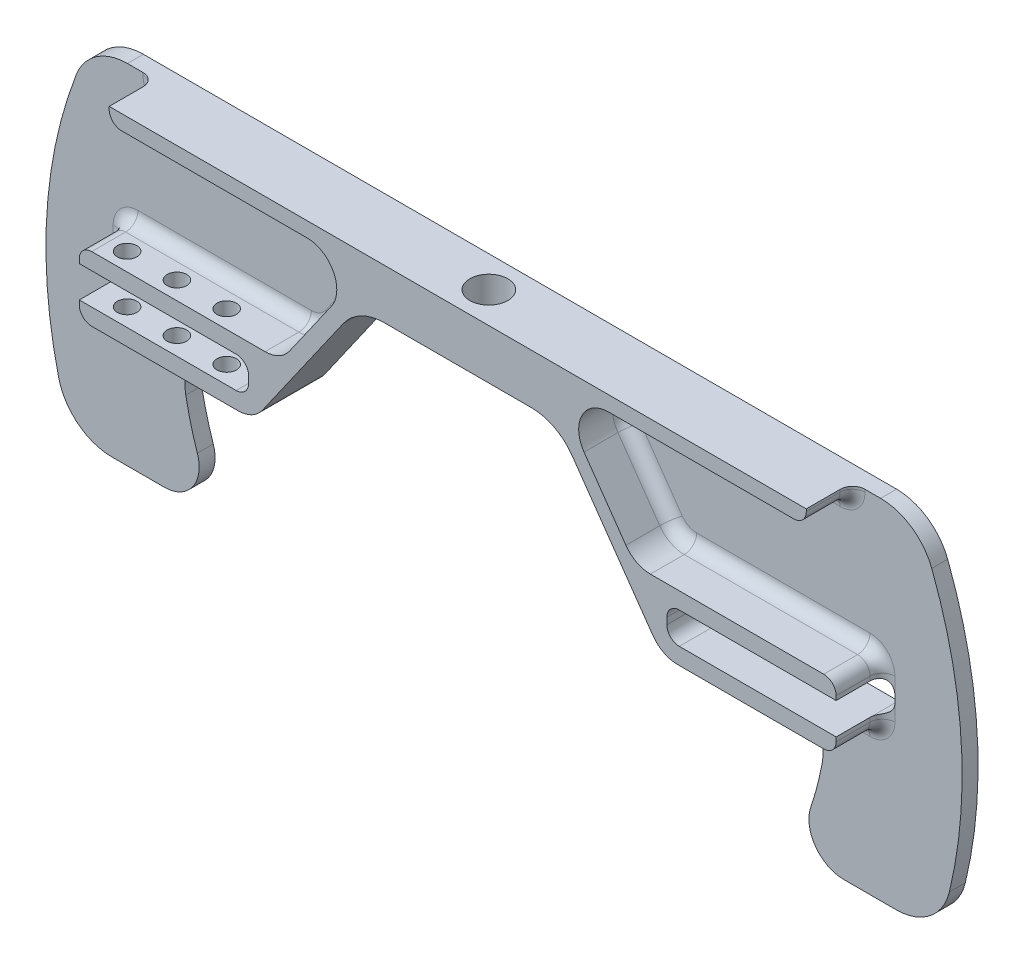
SolidWorks part; units mm, degrees
material "6061-T6 (SS)"
ref_plane "Front Plane" through (0, 0, 0) normal (0, 0, 1) x (1, 0, 0)
ref_plane "Top Plane" through (0, 0, 0) normal (0, 1, 0) x (1, 0, 0)
ref_plane "Right Plane" through (0, 0, 0) normal (1, 0, 0) x (0, 0, -1)
sketch "Outline" plane through (0, 0, 0) normal (0, 0, 1) x (1, 0, 0)
  line L0 (-127, 0) -> (127, 0) construction
  line L1 (0, 0) -> (0, 50.8) construction
  line L2 (-127, 38.1) -> (127, 38.1) construction
  line L3 (0, 0) -> (0, -38.1) construction
  line L4 (-127, 16.51) -> (127, 16.51) construction
  line L5 (-127, -38.1) -> (127, -38.1) construction
  line L6 (63.5, 139.7) -> (63.5, -139.7) construction
  line L7 (76.2, 139.7) -> (76.2, -139.7) construction
  line L8 (88.9, 139.7) -> (88.9, -139.7) construction
  line L9 (-127, 50.8) -> (127, 50.8) construction
  line L10 (-88.9, 139.7) -> (-88.9, -139.7) construction
  line L11 (-76.2, 139.7) -> (-76.2, -139.7) construction
  line L12 (-63.5, 139.7) -> (-63.5, -139.7) construction
  circle A0 centre (0, 0) radius 127 construction
  circle A1 centre (0, 0) radius 116.84 construction
  circle A2 centre (0, 0) radius 76.2 construction
  point P9 (0, 38.1)
  point P13 (0, 16.51)
  point P17 (0, -38.1)
  point P20 (63.5, 0)
  point P25 (76.2, 0)
  point P26 (88.9, 0)
  point P29 (0, 50.8)
  dimension "D1" = 254
  dimension "D2" = 233.68
  dimension "D7" = 152.4
  dimension "D3" = 50.8
  dimension "D4" = 38.1
  dimension "D5" = 38.1
  dimension "D6" = 16.51
  dimension "D8" = 279.4
  dimension "D9" = 63.5
  dimension "D10" = 12.7
  dimension "D11" = 12.7
sketch "Sketch" plane through (0, 0, 0) normal (0, 0, 1) x (1, 0, 0)
  line L0 (56.7961, 50.8) -> (105.2186, 50.8)
  line L2 (-127, 50.8) -> (127, 50.8) construction
  line L4 (65.9911, -38.1) -> (110.4535, -38.1)
  line L6 (-127, -38.1) -> (127, -38.1) construction
  line L7 (0, 50.8) -> (0, -38.1) construction
  line L8 (-65.9911, -38.1) -> (-110.4535, -38.1)
  line L9 (-56.7961, 50.8) -> (-105.2186, 50.8)
  arc A0 (65.9911, -38.1) -> (56.7961, 50.8) centre (0, 0) ccw
  arc A3 (110.4535, -38.1) -> (105.2186, 50.8) centre (0, 0) ccw
  circle A4 centre (0, 0) radius 116.84 construction
  circle A5 centre (0, 0) radius 76.2 construction
  arc A6 (-110.4535, -38.1) -> (-105.2186, 50.8) centre (0, 0) cw
  arc A7 (-65.9911, -38.1) -> (-56.7961, 50.8) centre (0, 0) cw
extrude "Pad" add sketch "Sketch" along normal blind 4.064
sketch "Sketch1" plane through (0, 0, 0) normal (0, 0, 1) x (1, 0, 0)
  line L2 (-127, 50.8) -> (127, 50.8) construction
  line L3 (-88.9, 50.8) -> (88.9, 50.8)
  line L4 (-88.9, 50.8) -> (-88.9, 46.99)
  line L5 (-88.9, 46.99) -> (88.9, 46.99)
  line L7 (88.9, 50.8) -> (88.9, 46.99)
  line L8 (0, 0) -> (0, 50.8) construction
  point P6 (0, 50.8)
  dimension "D1" = 177.8
  dimension "D2" = 3.81
extrude "Upper Bar" add sketch "Sketch1" along normal blind 15.875
sketch "Sketch2" plane through (0, 0, 0) normal (0, 0, 1) x (1, 0, 0)
  line L1 (-127, 50.8) -> (127, 50.8) construction
  line L2 (0, 0) -> (0, 50.8) construction
  line L3 (-25.4, 38.1) -> (25.4, 38.1)
  line L4 (-21.1585, 50.8) -> (21.1585, 50.8)
  line L5 (-127, 38.1) -> (127, 38.1) construction
  line L7 (-25.4, 38.1) -> (-52.0779, 0)
  line L8 (-127, 0) -> (127, 0) construction
  line L9 (-52.0779, 0) -> (-96.52, 0)
  line L10 (-96.52, 0) -> (-96.52, 16.51)
  line L11 (-127, 16.51) -> (127, 16.51) construction
  line L12 (-96.52, 16.51) -> (-45.1686, 16.51)
  line L13 (-45.1686, 16.51) -> (-21.1585, 50.8)
  line L14 (0, 50.8) -> (0, 38.1)
  line L15 (0, 0) -> (0, -38.1) construction
  line L16 (0, 50.8) -> (0, -38.1) construction
  line L17 (96.52, 0) -> (96.52, 16.51)
  line L18 (52.0779, 0) -> (96.52, 0)
  line L19 (25.4, 38.1) -> (52.0779, 0)
  line L20 (45.1686, 16.51) -> (21.1585, 50.8)
  line L21 (96.52, 16.51) -> (45.1686, 16.51)
  dimension "D1" = 25.4
  dimension "D2" = 125
  dimension "D3" = 3.81
  dimension "D4" = 96.52
extrude "Lower Bar" add sketch "Sketch2" along normal blind 15.875 contours L12 L13 L4 L20 L21 L17 L18 L19 L3 L7 L9 L10
sketch "Sketch4" plane through (0, 0, 0) normal (0, 0, 1) x (1, 0, 0)
  line L0 (-99.695, 12.2682) -> (-53.34, 12.2682)
  line L1 (-53.34, 12.2682) -> (-53.34, 4.2418)
  line L2 (-53.34, 4.2418) -> (-99.695, 4.2418)
  line L3 (-99.695, 4.2418) -> (-99.695, 12.2682)
  line L4 (0, 50.8) -> (0, -38.1) construction
  line L5 (-99.695, 8.255) -> (-53.34, 8.255) construction
  line L6 (-127, 0) -> (127, 0) construction
  line L7 (99.695, 4.2418) -> (99.695, 12.2682)
  line L8 (53.34, 4.2418) -> (99.695, 4.2418)
  line L9 (53.34, 12.2682) -> (53.34, 4.2418)
  line L10 (99.695, 12.2682) -> (53.34, 12.2682)
  dimension "D1" = 8.255
  dimension "D2" = 53.34
  dimension "D3" = 46.355
  dimension "D4" = 8.0264
extrude "Cut Lower Bar" cut sketch "Sketch4" along normal through all
fillet "Fillet1" radius 13.97 4 edges at (-105.2186, 50.8, 2.032) (105.2186, 50.8, 2.032) (110.4535, -38.1, 2.032) (-110.4535, -38.1, 2.032)
sketch "Sketch5" plane through (0, 0, 0) normal (0, 0, -1) x (-1, 0, 0)
  line L0 (-23.8263, 46.99) -> (-59.9865, 46.99) construction
  line L1 (-45.1686, 16.51) -> (-23.8263, 46.99) construction
  line L2 (127, 16.51) -> (-127, 16.51) construction
  line L3 (45.1686, 16.51) -> (23.8263, 46.99) construction
  line L4 (59.9865, 46.99) -> (23.8263, 46.99) construction
  line L5 (-23.8263, 46.99) -> (-59.9865, 46.99)
  line L6 (-45.1686, 16.51) -> (-23.8263, 46.99)
  line L7 (127, 16.51) -> (-127, 16.51)
  line L8 (45.1686, 16.51) -> (23.8263, 46.99)
  line L9 (59.9865, 46.99) -> (23.8263, 46.99)
  circle A0 centre (0, 0) radius 76.2 construction
  circle A1 centre (0, 0) radius 76.2
  line M5 (45.1686, 16.51) -> (23.8263, 46.99)
  line M6 (23.8263, 46.99) -> (59.9865, 46.99)
  arc M7 (59.9865, 46.99) -> (74.3899, 16.51) centre (0, 0) cw
  line M8 (74.3899, 16.51) -> (45.1686, 16.51)
  line M9 (-45.1686, 16.51) -> (-74.3899, 16.51)
  arc M10 (-74.3899, 16.51) -> (-59.9865, 46.99) centre (0, 0) cw
  line M11 (-59.9865, 46.99) -> (-23.8263, 46.99)
  line M12 (-23.8263, 46.99) -> (-45.1686, 16.51)
extrude "Boss-Extrude4" add sketch "Sketch5" against normal blind 4.064 contours M9 M12 M11 M10 | M5 M8 M7 M6 region at (51.2368, 32.2803, 0) region at (-51.2368, 32.2803, 0)
sketch "Sketch6" plane through (0, 0, 0) normal (0, 0, -1) x (-1, 0, 0)
  line L0 (-82.55, 0) -> (82.55, 0)
  arc A0 (-82.55, 0) -> (82.55, 0) centre (0, 0) ccw
  point P2 (0, 0)
  dimension "D1" = 165.1
extrude "Cut-Extrude2" cut sketch "Sketch6" against normal blind 4.572
fillet "Fillet3" radius 8.89 2 edges at (73.2318, -38.1, 2.032) (-73.2318, -38.1, 2.032)
fillet "Fillet4" radius 12.7 4 edges at (-25.4, 38.1, 7.9375) (25.4, 38.1, 7.9375) (-82.55, 0, 2.032) (82.55, 0, 2.032)
fillet "Fillet5" radius 7.62 2 edges at (-52.0779, 0, 7.9375) (52.0779, 0, 7.9375)
fillet "Fillet6" radius 3.175 8 edges at (-53.34, 4.2418, 7.9375) (-53.34, 12.2682, 7.9375) (-99.695, 12.2682, 2.032) (-99.695, 4.2418, 2.032) (53.34, 4.2418, 7.9375) (99.695, 4.2418, 2.032) (53.34, 12.2682, 7.9375) (99.695, 12.2682, 2.032)
fillet "Fillet7" radius 7.62 4 edges at (23.8263, 46.99, 9.9695) (-23.8263, 46.99, 9.9695) (45.1686, 16.51, 9.9695) (-45.1686, 16.51, 9.9695)
fillet "Fillet9" radius 3.175 24 edges at (88.9, 48.895, 4.064) (63.6821, 46.99, 4.064) (31.7052, 42.8885, 4.064) (37.5578, 27.3793, 4.064) (45.6168, 17.371, 4.064) (72.8277, 16.51, 4.064) (-45.6168, 17.371, 4.064) (-37.5578, 27.3793, 4.064) (-31.7052, 42.8885, 4.064) (88.9, 46.99, 9.9695) (96.52, 0, 9.9695) (96.52, 16.51, 9.9695) (96.52, 14.3891, 4.064) (-88.9, 46.99, 9.9695) (-96.52, 16.51, 9.9695) (-96.52, 0, 9.9695) (-88.9, 48.895, 4.064) (-96.52, 14.3891, 4.064) (-72.8277, 16.51, 4.064) (-63.6821, 46.99, 4.064) (96.52, 2.1209, 4.064) (82.6029, 0, 4.064) (-96.52, 2.1209, 4.064) (-82.6029, 0, 4.064)
sketch "Sketch9" plane through (0, 0, 0) normal (0, -1, 0) x (1, 0, 0)
  line L0 (0, 16.51) -> (0, 0) construction
  line L1 (-93.345, 11.303) -> (-56.0446, 11.303) construction
  line L2 (-93.345, 15.875) -> (-93.345, 7.239) construction
  line L3 (-56.0446, 0) -> (-56.0446, 15.875) construction
  line L4 (-56.0446, 15.875) -> (-93.345, 15.875) construction
  line L5 (-127, 0) -> (127, 0) construction
  circle A0 centre (-63.5, 11.303) radius 2.4892
  circle A1 centre (-76.2, 11.303) radius 2.4892
  circle A2 centre (-88.9, 11.303) radius 2.4892
  point P9 (-63.5, 11.303)
  point P10 (-76.2, 11.303)
  point P11 (-88.9, 11.303)
  dimension "D6" = 4.9784
  dimension "D1" = 63.5
  dimension "D2" = 12.7
  dimension "D3" = 12.7
  dimension "D4" = 4.572
  dimension "D5" = 16.51
extrude "Three Holes" cut sketch "Sketch9" against normal up to surface (16.51 mm away) up to face at (-71.2402, 16.51, 11.557)
sketch "Sketch14" plane through (0, 38.1, 0) normal (0, -1, 0) x (1, 0, 0)
  line L0 (0, 0) -> (0, 15.875) construction
  line L1 (-18.7888, 15.875) -> (18.7888, 15.875) construction
  circle A0 centre (0, 7.9375) radius 4.8387
  point P7 (0, 7.9375)
  dimension "D1" = 9.6774
extrude "Big Hole" cut sketch "Sketch14" against normal through all
